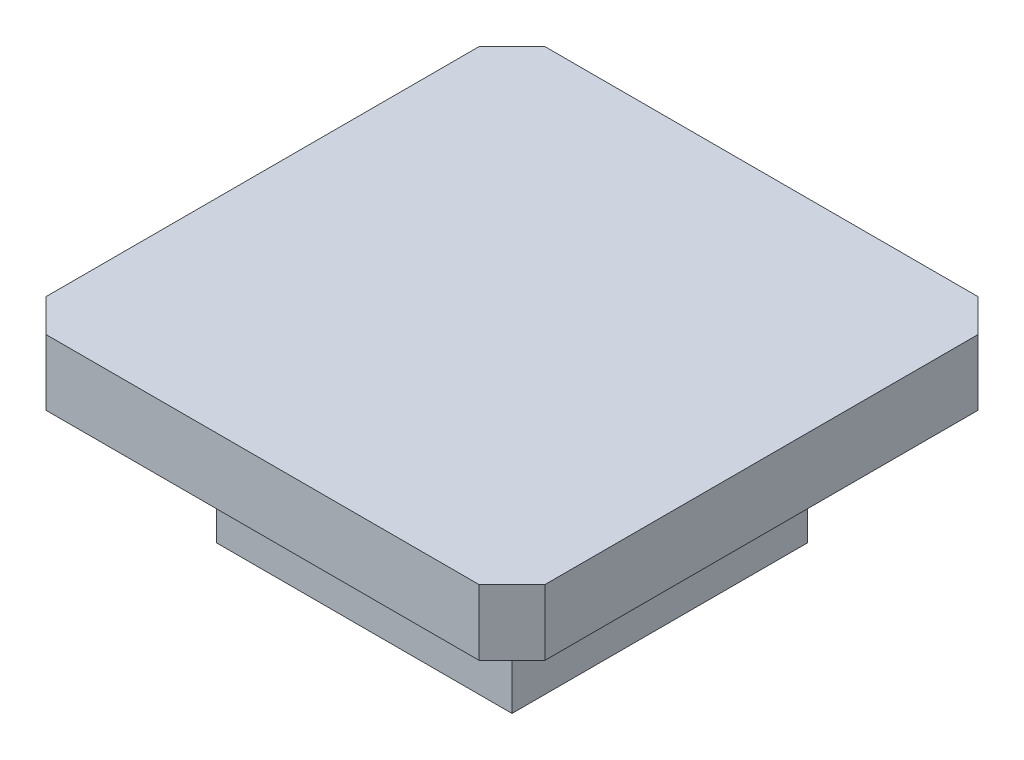
SolidWorks part; units mm, degrees
material "2024-T3"
ref_plane "Front Plane" through (0, 0, 0) normal (0, 0, 1) x (1, 0, 0)
ref_plane "Top Plane" through (0, 0, 0) normal (0, 1, 0) x (1, 0, 0)
ref_plane "Right Plane" through (0, 0, 0) normal (1, 0, 0) x (0, 0, -1)
sketch "Sketch1" plane through (0, 0, 0) normal (0, 1, 0) x (1, 0, 0)
  line L1 (0, 0) -> (48.26, 0)
  line L2 (0, 0) -> (0, 48.26)
  line L3 (0, 48.26) -> (48.26, 48.26)
  line L4 (48.26, 0) -> (48.26, 48.26)
  dimension "D1" = 48.26
  dimension "D2" = 48.26
extrude "Boss-Extrude1" add sketch "Sketch1" along normal blind 6.35
chamfer "Chamfer1" distance 3.175 angle 45 4 edges at (48.26, 3.175, -48.26) (0, 3.175, -48.26) (0, 3.175, 0) (48.26, 3.175, 0)
sketch "Sketch4" plane through (0, 0, 0) normal (0, -1, 0) x (1, 0, 0)
  line L0 (1.5875, -1.5875) -> (46.6725, -46.6725) construction
  line L1 (3.175, 0) -> (0, -3.175) construction
  line L2 (45.085, -48.26) -> (48.26, -45.085) construction
  line L4 (9.8425, -38.4175) -> (38.4175, -38.4175)
  line L5 (9.8425, -38.4175) -> (9.8425, -9.8425)
  line L6 (9.8425, -9.8425) -> (38.4175, -9.8425)
  line L7 (38.4175, -38.4175) -> (38.4175, -9.8425)
  line L8 (9.8425, -38.4175) -> (38.4175, -9.8425) construction
  line L9 (9.8425, -9.8425) -> (38.4175, -38.4175) construction
  point P6 (24.13, -24.13)
  dimension "D1" = 28.575
extrude "Boss-Extrude2" add sketch "Sketch4" along normal blind 12.7
chamfer "Chamfer2" distance 1.5875 angle 45 4 edges at (24.13, 0, -9.8425) (38.4175, 0, -24.13) (24.13, 0, -38.4175) (9.8425, 0, -24.13)
ref_point "Point3"
ref_point "Point4"
ref_axis "Axis2" through (24.13, 6.35, -24.13) along (0, -1, 0)
